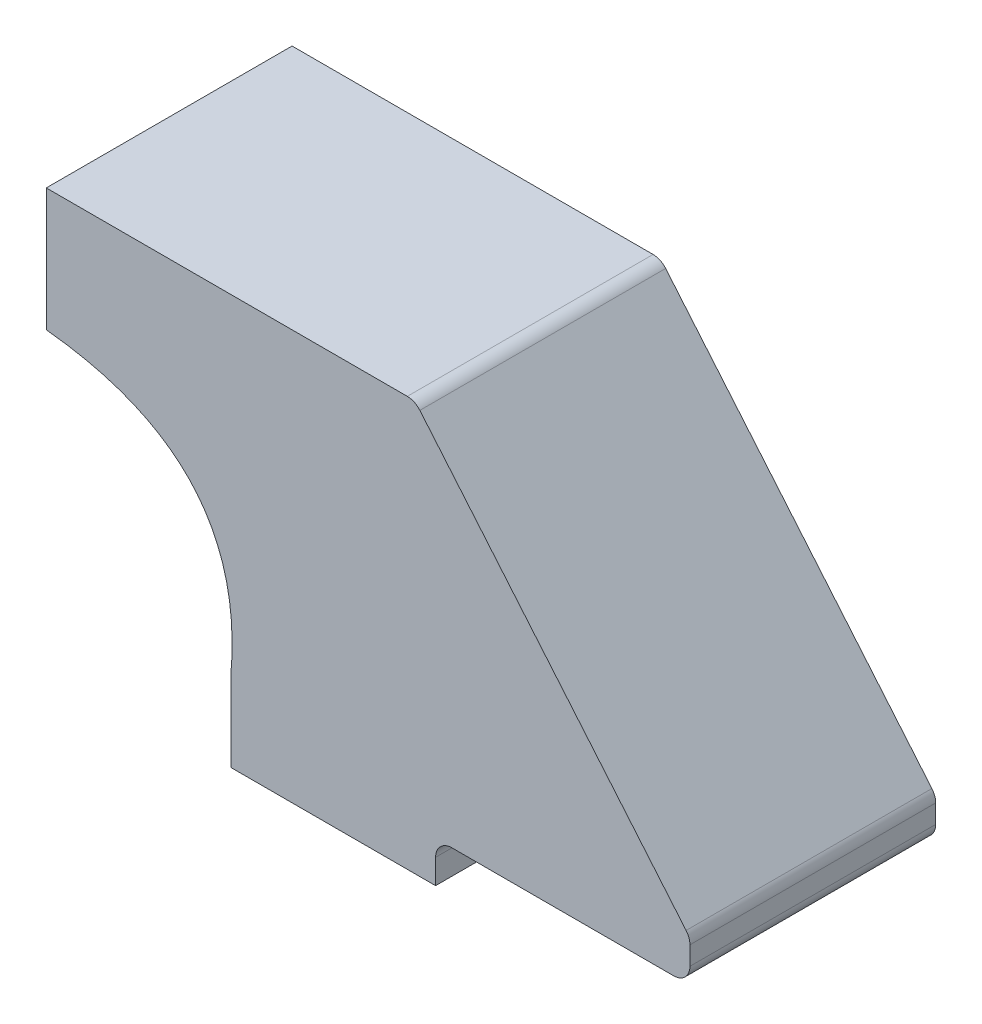
SolidWorks part; units mm, degrees
ref_plane "Front Plane" through (0, 0, 0) normal (0, 0, 1) x (1, 0, 0)
ref_plane "Top Plane" through (0, 0, 0) normal (0, 1, 0) x (1, 0, 0)
ref_plane "Right Plane" through (0, 0, 0) normal (1, 0, 0) x (0, 0, -1)
sketch "Sketch1" plane through (0, 0, 0) normal (0, 0, 1) x (1, 0, 0)
  line L0 (-28.5977, 0) -> (27.3678, 0)
  line L12 (-28.5977, 0) -> (-28.5977, -19.05)
  line L14 (0, -51.2256) -> (0, -63.5)
  line L15 (0, -63.5) -> (31.75, -63.5)
  line L17 (29.3136, -0.9073) -> (70.5843, -50.0918)
  line L18 (71.1785, -51.7245) -> (71.1785, -54.61)
  line L19 (68.6385, -57.15) -> (34.29, -57.15)
  line L20 (31.75, -63.5) -> (31.75, -59.69)
  arc A0 (31.75, -59.69) -> (34.29, -57.15) centre (34.29, -59.69) cw
  arc A1 (71.1785, -54.61) -> (68.6385, -57.15) centre (68.6385, -54.61) cw
  arc A2 (70.5843, -50.0918) -> (71.1785, -51.7245) centre (68.6385, -51.7245) cw
  arc A3 (27.3678, 0) -> (29.3136, -0.9073) centre (27.3678, -2.54) cw
  spline S2 degree 2 poles (-28.5977, -19.05) (2.6999, -22.2822) (0, -51.2256) knots 0 0 0 1 1 1
  point P12 (31.75, -57.15)
  point P15 (71.1785, -57.15)
  point P20 (71.1785, -50.8)
  point P24 (28.5523, 0)
  dimension "D8" = 2.54
  dimension "D1" = 19.05
  dimension "D2" = 31.75
  dimension "D3" = 50
  dimension "D4" = 57.15
  dimension "D5" = 6.35
  dimension "D6" = 63.5
  dimension "D7" = 6.35
extrude "Boss-Extrude1" add sketch "Sketch1" along normal blind 38.1
shell "Shell1" thickness 2.54 removed face at (0, -57.3628, 19.05) removed face at (-21.4483, -27.0939, 19.05)
ref_plane "Plane1" through (33.02, 0, 0) normal (-1, 0, 0) x (0, 0, 1)
sketch "Sketch2" plane through (33.02, 0, 0) normal (-1, 0, 0) x (0, 0, 1)
  line L1 (0, -19.05) -> (0, -51.2256) construction
  line L2 (38.1, -63.5) -> (0, -63.5) construction
  circle A0 centre (19.05, -31.75) radius 9.525
  circle A1 centre (19.05, -31.75) radius 6.35
  point P3 (0, 0)
  dimension "D1" = 19.05
  dimension "D2" = 12.7
  dimension "D3" = 19.05
  dimension "D4" = 31.75
extrude "Boss-Extrude2" add sketch "Sketch2" along normal blind 35.56 and the other way up to surface other way up to face at (48.0032, -27.1322, 19.05)
ref_plane "Plane2" through (29.21, -60.96, 2.54) normal (1, 0, 0) x (0, 0, -1)
